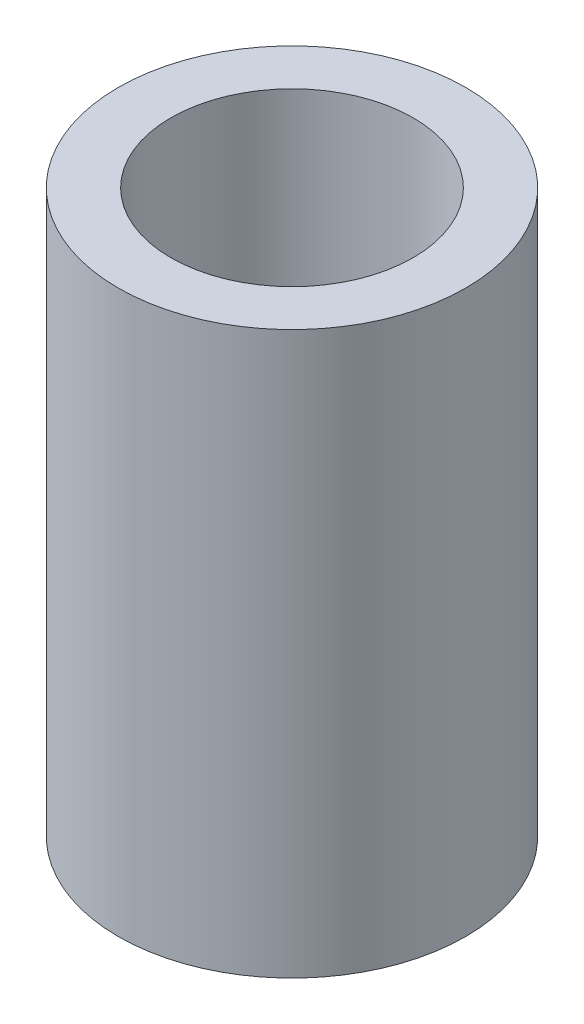
SolidWorks part; units mm, degrees
material "Thread"
ref_plane "Front Plane" through (0, 0, 0) normal (0, 0, 1) x (1, 0, 0)
ref_plane "Top Plane" through (0, 0, 0) normal (0, 1, 0) x (1, 0, 0)
ref_plane "Right Plane" through (0, 0, 0) normal (1, 0, 0) x (0, 0, -1)
ref_plane "Plane1" through (0, 23.2214, 0) normal (0, -1, 0) x (-1, 0, 0)
ref_plane "Plane2" through (0, -20.2126, 0) normal (0, 1, 0) x (1, 0, 0)
sketch "Sketch1" plane through (0, 23.2214, 0) normal (0, -1, 0) x (1, 0, 0)
  circle A0 centre (-4.0978, 0.3551) radius 13.4366 construction
  circle A1 centre (-4.0978, 0.3551) radius 13.4366
  circle A2 centre (-4.0978, 0.3551) radius 9.3726 construction
  circle A3 centre (-4.0978, 0.3551) radius 9.3726
extrude "Boss-Extrude1" add sketch "Sketch1" along normal up to surface (43.434 mm away) up to plane "Plane2"
